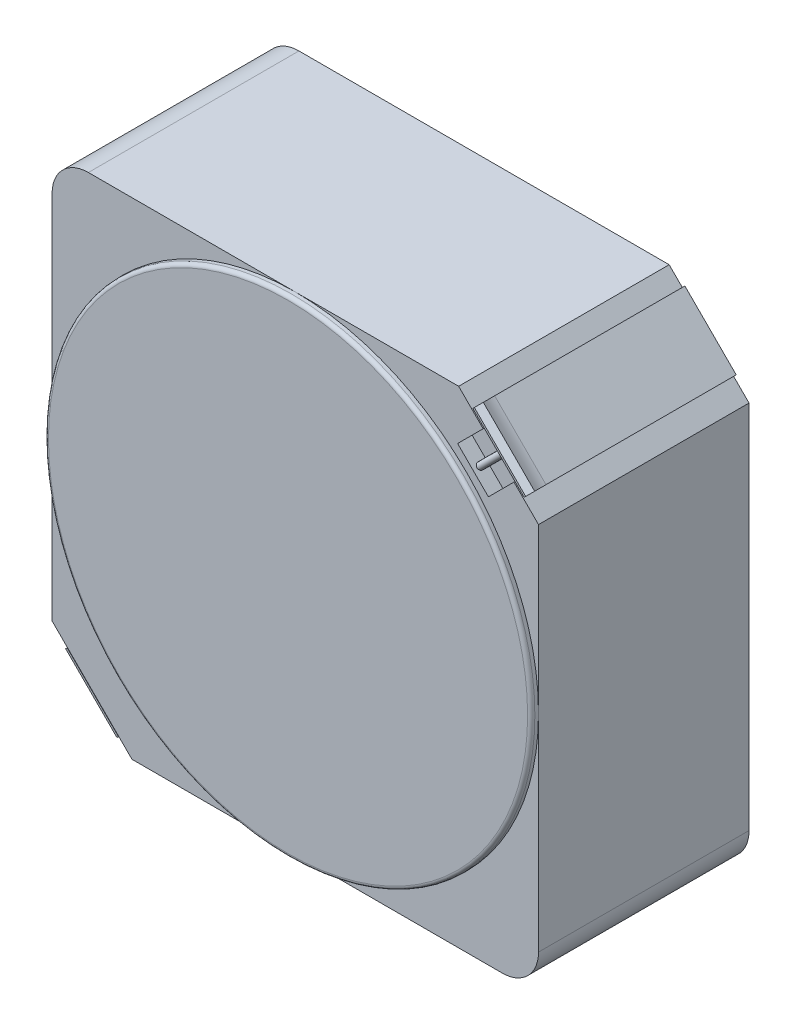
SolidWorks part; units mm, degrees
ref_plane "Спереди" through (0, 0, 0) normal (0, 0, 1) x (1, 0, 0)
ref_plane "Сверху" through (0, 0, 0) normal (0, 1, 0) x (1, 0, 0)
ref_plane "Справа" through (0, 0, 0) normal (1, 0, 0) x (0, 0, -1)
sketch "Эскиз1" plane through (0, 0, 0) normal (0, 0, 1) x (1, 0, 0)
  line L0 (-3.35, -2.25) -> (-2.25, -3.35)
  line L1 (-2.85, 3.35) -> (2.25, 3.35)
  line L2 (-3.35, 2.85) -> (-3.35, -2.25)
  line L3 (-2.25, -3.35) -> (2.85, -3.35)
  line L4 (3.35, 2.25) -> (3.35, -2.85)
  line L5 (-3.35, 3.35) -> (3.35, -3.35) construction
  line L6 (-3.35, -3.35) -> (3.35, 3.35) construction
  line L7 (2.25, 3.35) -> (3.35, 2.25)
  arc A0 (-2.85, 3.35) -> (-3.35, 2.85) centre (-2.85, 2.85) ccw
  arc A1 (2.85, -3.35) -> (3.35, -2.85) centre (2.85, -2.85) ccw
  point P0 (0, 0)
  dimension "D1" = 0.5
  dimension "D2" = 6.7
extrude "Корпус" add sketch "Эскиз1" along normal blind 2.9 from offset 0.005
sketch "Эскиз2" plane through (0, 0, 2.905) normal (0, 0, 1) x (1, 0, 0)
  line L0 (-3.35, 2.85) -> (-3.35, -2.25) construction
  circle A0 centre (0, 0) radius 3.35
extrude "Сердечник" add sketch "Эскиз2" along normal blind 0.1 and the other way blind 1
fillet "Скругление1" radius 0.05 1 edges at (3.35, 0, 3.005)
ref_plane "Плоскость1" through (0.55, -0.55, 0) normal (0.7071, -0.7071, 0) x (0, 0, 1)
sketch "Эскиз6" plane through (0.55, -0.55, 0) normal (0.7071, -0.7071, 0) x (0, 0, 1)
  line L0 (2.813, -4.0548) -> (2.9, -4.0028)
  line L1 (2.9, -3.9728) -> (0.03, -3.9728)
  line L2 (2.62, -4.0028) -> (0, -4.0028)
  line L3 (0, -4.0028) -> (0, -3.4728)
  line L4 (0.03, -3.9728) -> (0.03, -3.4728)
  line L5 (0.03, -3.4728) -> (0, -3.4728)
  line L6 (2.9, -4.0028) -> (2.9, -3.9728)
  line L8 (0.005, -3.9598) -> (2.905, -3.9598) construction
  line L9 (2.905, -3.35) -> (2.905, -2.3688) construction
  line L11 (0.005, 0.3536) -> (0.005, 3.9598) construction
  line L12 (2.905, -3.9598) -> (0.005, -3.9598) construction
  spline S0 degree 2 poles (2.62, -4.0028) (2.7238, -4.0066) (2.813, -4.0548) knots 0 0 0 1 1 1
  dimension "D2" = 0.5
  dimension "D3" = 0.013
  dimension "D4" = 0.025
  dimension "D5" = 0.005
  dimension "D6" = 0.082
  dimension "D7" = 0.087
  dimension "D8" = 120.867
  dimension "D9" = 0.28
  dimension "D10" = 0.1354
  dimension "D11" = 0.0295
  dimension "D12" = 0.03
extrude "вывод, бок" add sketch "Эскиз6" against normal blind 1 from offset 0.3 offset against normal yes
ref_point "Точка1"
ref_axis "Ось1" through (0, 0, 3.005) along (0, 0, -1)
sketch "Эскиз8" plane through (0, 0, 2.905) normal (0, 0, 1) x (1, 0, 0)
  line L0 (3.0121, 2.5879) -> (2.5879, 3.0121)
  line L2 (2.5879, 3.0121) -> (2.2357, 2.66)
  line L3 (-1.6879, -2.1121) -> (-1.3487, -1.7475)
  line L4 (2.4479, 2.4479) -> (0, 0) construction
  line L5 (3.0121, 2.5879) -> (2.66, 2.2357)
  line L6 (2.66, 2.2357) -> (2.2357, 2.66)
  line L7 (-1.788, -1.3388) -> (-1.3487, -1.7475)
  line L8 (-2.1272, -1.7034) -> (-1.788, -1.3388)
  line L9 (-2.1272, -1.7034) -> (-1.6879, -2.1121)
  line L10 (3.35, 2.25) -> (2.25, 3.35) construction
  dimension "D2" = 0.498
  dimension "D4" = 0.6
  dimension "D1" = 2
extrude "Вытянуть8" cut sketch "Эскиз8" against normal blind 0.2
sketch "Эскиз9" plane through (2.8092, 2.8092, 0) normal (-0.7071, -0.7071, 0) x (0, 0, 1)
  line L1 (0, 0) -> (2.804, 0) construction
  line L2 (2.9, 0.5222) -> (2.9, -0.4778) construction
  circle A0 centre (2.804, 0) radius 0.046
  dimension "D1" = 0.092
  dimension "D2" = 0.096
extrude "Бобышка-Вытянуть1" add sketch "Эскиз9" along normal up to next (0.511 mm away) and the other way blind 0.05 draft 45 from offset 0.05 other way draft outward yes
pattern_circular "Круговой массив3" count 2 over 360 about axis through (0, 0, 3.005) along (0, 0, -1) of "вывод, бок", "Бобышка-Вытянуть1"
sketch "Эскиз13" plane through (0, 0, 0.005) normal (0, 0, -1) x (-1, 0, 0)
  line L1 (-3.35, -2.85) -> (-3.35, 2.25) construction
  line L2 (0, -3.3) -> (0, 0) construction
  line L3 (3.35, 2.85) -> (3.35, -2.25) construction
  line L4 (2.4308, -3.1692) -> (2.25, -3.35) construction
  line L5 (1.6527, 0) -> (-1.6527, 0) construction
  line L6 (2.3246, 1.6488) -> (3.3, 1.6488)
  line L7 (2.25, -3.35) -> (-2.85, -3.35) construction
  line L8 (3.3, 1.6488) -> (3.3, 2.2288)
  line L9 (2.2288, 3.3) -> (3.3, 2.2288)
  line L10 (-2.2288, 3.3) -> (2.2288, 3.3)
  line L11 (-3.3, 2.2288) -> (-2.2288, 3.3)
  line L12 (-3.3, -1.6488) -> (-2.3246, -1.6488)
  line L13 (-3.3, -2.2288) -> (-3.3, -1.6488)
  line L16 (-3.3, -2.2288) -> (-2.2288, -3.3)
  line L17 (-3.3, 2.2288) -> (-3.3, 1.6488)
  line L18 (-2.2288, -3.3) -> (2.2288, -3.3)
  line L19 (2.2288, -3.3) -> (3.3, -2.2288)
  line L20 (3.3, -1.6488) -> (3.3, -2.2288)
  line L21 (2.3246, -1.6488) -> (3.3, -1.6488)
  line L22 (-3.3, 1.6488) -> (-2.3246, 1.6488)
  arc A0 (-2.3246, -1.6488) -> (2.3246, -1.6488) centre (0, 0) ccw
  arc A1 (-2.3246, 1.6488) -> (2.3246, 1.6488) centre (0, 0) cw
  circle A2 centre (0, 0) radius 3.35 construction
  dimension "D2" = 0.5
  dimension "D3" = 0.9754
  dimension "D5" = 0.05
  dimension "D6" = 0.0503
  dimension "D7" = 0.05
  dimension "D1" = 0.58
extrude "Выводы низ" add sketch "Эскиз13" along normal up to surface (0.005 mm away) up to face at (-2.6273, -2.6587, 0)
